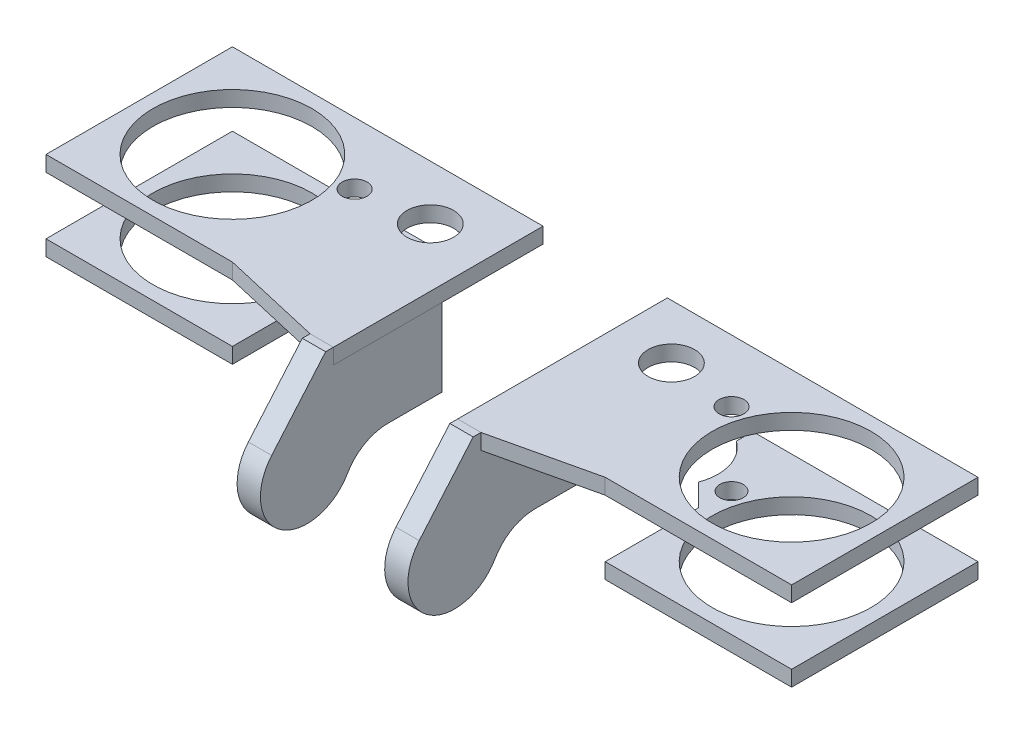
SolidWorks part; units mm, degrees
ref_plane "Front Plane" through (0, 0, 0) normal (0, 0, 1) x (1, 0, 0)
ref_plane "Top Plane" through (0, 0, 0) normal (0, 1, 0) x (1, 0, 0)
ref_plane "Right Plane" through (0, 0, 0) normal (1, 0, 0) x (0, 0, -1)
sketch "Sketch1" plane through (0, 0, 0) normal (0, 1, 0) x (1, 0, 0)
  line L0 (0, 0) -> (114.3, 0) construction
  line L1 (-114.3, 0) -> (0, 0) construction
  line L3 (-9.525, 184.15) -> (-3.175, 184.15)
  line L4 (-9.525, 184.15) -> (-9.525, 69.85)
  line L5 (-9.525, 69.85) -> (-3.175, 69.85)
  line L6 (-3.175, 184.15) -> (-3.175, 69.85)
  line L7 (-9.525, 184.15) -> (-3.175, 69.85) construction
  line L8 (-9.525, 69.85) -> (-3.175, 184.15) construction
  line L14 (-152.4, -76.2) -> (152.4, -76.2)
  line L18 (-114.3, 0) -> (-49.2756, 15.875) construction
  line L19 (49.2756, 15.875) -> (114.3, 0) construction
  line L20 (-25.4, 38.1) -> (0, 38.1) construction
  line L21 (-6.35, 127) -> (0, 127)
  line L29 (0, 0) -> (0, -25.4) construction
  line L30 (-114.3, 0) -> (-77.0346, 12.7) construction
  line L43 (-77.0346, 12.7) -> (-49.2756, 15.875) construction
  line L44 (49.2756, 15.875) -> (77.0346, 12.7) construction
  line L55 (77.0346, 12.7) -> (114.3, 0) construction
  line L69 (-152.4, -76.2) -> (-152.4, 38.1)
  line L70 (-152.4, 38.1) -> (152.4, 38.1)
  line L71 (152.4, -76.2) -> (152.4, 38.1)
  line L78 (0, 127) -> (0, -25.4)
  line L79 (0, -25.4) -> (0, -177.8) construction
  line L80 (-9.525, -234.95) -> (-3.175, -234.95) construction
  line L81 (-9.525, -234.95) -> (-9.525, -120.65) construction
  line L82 (-9.525, -120.65) -> (-3.175, -120.65) construction
  line L83 (-3.175, -234.95) -> (-3.175, -120.65) construction
  line L84 (-9.525, -234.95) -> (-3.175, -120.65) construction
  line L85 (-9.525, -120.65) -> (-3.175, -234.95) construction
  line L86 (0, -177.8) -> (-6.35, -177.8) construction
  line L87 (-34.925, -76.2) -> (-25.4, -76.2)
  line L88 (-34.925, -76.2) -> (-34.925, 38.1)
  line L89 (-34.925, 38.1) -> (-25.4, 38.1)
  line L90 (-25.4, -76.2) -> (-25.4, 38.1)
  line L91 (34.925, -76.2) -> (25.4, -76.2)
  line L92 (34.925, -76.2) -> (34.925, 38.1)
  line L93 (34.925, 38.1) -> (25.4, 38.1)
  line L94 (25.4, -76.2) -> (25.4, 38.1)
  line L95 (0, 38.1) -> (25.4, 38.1) construction
  circle A0 centre (-114.3, 0) radius 32.5
  circle A1 centre (-114.3, 0) radius 25
  circle A2 centre (114.3, 0) radius 32.5
  circle A3 centre (114.3, 0) radius 25
  circle A4 centre (-49.2756, 15.875) radius 17.5006
  circle A5 centre (49.2756, 15.875) radius 17.5006
  circle A6 centre (-77.0346, 12.7) radius 22.86
  circle A7 centre (77.0346, 12.7) radius 22.86
  point P8 (-6.35, 127)
  point P21 (114.3, 32.5)
  point P25 (49.2756, 33.3756)
  point P29 (49.2756, -1.6256)
  point P31 (0, -76.2)
  point P32 (-6.35, -177.8)
  point P62 (146.8, 0)
  dimension "D1" = 50
  dimension "D2" = 65
  dimension "D8" = 35.0012
  dimension "D11" = 152.4
  dimension "D12" = 63.5
  dimension "D17" = 45.72
  dimension "D3" = 114.3
  dimension "D4" = 6.35
  dimension "D5" = 228.6
  dimension "D6" = 38.1
  dimension "D7" = 38.1
  dimension "D9" = 114.3
  dimension "D10" = 9.525
  dimension "D13" = 9.525
  dimension "D14" = 50.8
  dimension "D15" = 27.94
  dimension "D16" = 39.37
  dimension "D18" = 22.225
  dimension "D19" = 25.4
sketch "Sketch2" plane through (0, 0, 0) normal (1, 0, 0) x (0, 0, -1)
  line L0 (0, 22.225) -> (0, 49.825) construction
  line L1 (-32.5, 53.325) -> (32.5, 53.325)
  line L2 (-32.5, 53.325) -> (-32.5, 46.325)
  line L3 (-32.5, 46.325) -> (32.5, 46.325)
  line L4 (32.5, 53.325) -> (32.5, 46.325)
  line L5 (-32.5, 53.325) -> (32.5, 46.325) construction
  line L6 (-32.5, 46.325) -> (32.5, 53.325) construction
  line L7 (-32.5, 82.55) -> (32.5, 82.55)
  line L8 (-32.5, 82.55) -> (-32.5, 75.55)
  line L9 (-32.5, 75.55) -> (32.5, 75.55)
  line L10 (32.5, 82.55) -> (32.5, 75.55)
  line L11 (-32.5, 82.55) -> (32.5, 75.55) construction
  line L12 (-32.5, 75.55) -> (32.5, 82.55) construction
  line L13 (-25.8191, 0) -> (33.9817, 0) construction
  line L14 (-25.4, 63.5) -> (-177.8, 63.5)
  line L15 (-76.2, 82.55) -> (38.1, 82.55)
  line L16 (-76.2, 82.55) -> (-76.2, 46.325)
  line L17 (-76.2, 46.325) -> (38.1, 46.325)
  line L18 (38.1, 82.55) -> (38.1, 46.325)
  line L19 (-25.4, 25.4) -> (-58.3956, 44.45) construction
  line L20 (-58.3956, 44.45) -> (-25.4, 63.5) construction
  line L21 (127, 0) -> (-25.4, 0) construction
  line L22 (-76.2, 76.2) -> (38.1, 76.2)
  line L23 (-76.2, 52.675) -> (38.1, 52.675)
  line L24 (-25.4, 25.4) -> (-25.4, 63.5) construction
  line L25 (-25.4, 7.62) -> (-25.4, 0) construction
  line L26 (32.5, 0) -> (-32.5, 0) construction
  line L40 (-1.6256, 31.6992) -> (33.3756, 31.6992)
  line L41 (-1.6256, 31.6992) -> (-1.6256, 76.2)
  line L42 (-1.6256, 76.2) -> (33.3756, 76.2)
  line L43 (33.3756, 31.6992) -> (33.3756, 76.2)
  line L44 (-1.6256, 31.6992) -> (33.3756, 76.2) construction
  line L45 (-1.6256, 76.2) -> (33.3756, 31.6992) construction
  line L46 (-38.1, 82.55) -> (-38.1, 46.325)
  line L47 (-38.1, 64.4375) -> (0, 64.4375) construction
  line L48 (0, 64.4375) -> (38.1, 64.4375) construction
  circle A0 centre (0, 22.225) radius 22.225
  circle A1 centre (-25.4, 63.5) radius 18.0086
  circle A2 centre (-25.4, 25.4) radius 17.78
  circle A3 centre (-177.8, 63.5) radius 57.15
  circle A4 centre (-25.4, 63.5) radius 4.7625
  circle A5 centre (-58.3956, 44.45) radius 17.78
  point P2 (0, 49.825)
  point P8 (0, 79.05)
  point P16 (-40.6156, 44.45)
  point P28 (-76.1756, 44.45)
  point P32 (15.875, 53.9496)
  point P34 (-234.95, 63.5)
  point P35 (-43.18, 25.4)
  point P36 (-7.62, 25.4)
  point P37 (-7.3914, 63.5)
  point P38 (-43.4086, 63.5)
  dimension "D1" = 44.45
  dimension "D8" = 36.0172
  dimension "D2" = 35.56
  dimension "D11" = 9.525
  dimension "D12" = 35.56
  dimension "D3" = 7
  dimension "D4" = 82.55
  dimension "D5" = 22.225
  dimension "D6" = 6.35
  dimension "D7" = 6.35
  dimension "D9" = 63.5
  dimension "D10" = 44.5008
  dimension "D13" = 38.1
  dimension "D14" = 38.1
  dimension "D15" = 38.1
sketch "Sketch5" plane through (0, 0, 0) normal (0, 1, 0) x (1, 0, 0)
  line L0 (-34.925, -76.2) -> (-34.925, 38.1) construction
  line L1 (-66.421, -7.62) -> (-34.925, -7.62)
  line L2 (-66.421, -7.62) -> (-66.421, -43.18)
  line L3 (-66.421, -43.18) -> (-34.925, -43.18)
  line L4 (-34.925, -7.62) -> (-34.925, -43.18)
  line L5 (-66.421, -7.62) -> (-34.925, -43.18) construction
  line L6 (-66.421, -43.18) -> (-34.925, -7.62) construction
  line L7 (-74.93, -40.6156) -> (-34.925, -40.6156)
  line L8 (-74.93, -40.6156) -> (-74.93, -76.1756)
  line L9 (-74.93, -76.1756) -> (-34.925, -76.1756)
  line L10 (-34.925, -40.6156) -> (-34.925, -76.1756)
  line L11 (-74.93, -40.6156) -> (-34.925, -76.1756) construction
  line L12 (-74.93, -76.1756) -> (-34.925, -40.6156) construction
  line L13 (-66.421, -7.3914) -> (-26.416, -7.3914)
  line L14 (-66.421, -7.3914) -> (-66.421, -43.4086)
  line L15 (-66.421, -43.4086) -> (-26.416, -43.4086)
  line L16 (-26.416, -7.3914) -> (-26.416, -43.4086)
  line L17 (-66.421, -7.3914) -> (-26.416, -43.4086) construction
  line L18 (-66.421, -43.4086) -> (-26.416, -7.3914) construction
  point P0 (-50.673, -25.4)
  point P5 (-54.9275, -58.3956)
  point P10 (-46.4185, -25.4)
  dimension "D2" = 31.496
  dimension "D5" = 40.005
  dimension "D6" = 40.005
ref_plane "Plane1" through (0, 76.2, 0) normal (0, 1, 0) x (1, 0, 0)
ref_plane "Plane2" through (0, 52.675, 0) normal (0, -1, 0) x (-1, 0, 0)
ref_plane "Plane3" through (25.4, 0, 0) normal (1, 0, 0) x (0, 0, -1)
sketch "Sketch6" plane through (25.4, 0, 0) normal (1, 0, 0) x (0, 0, -1)
  line L0 (-25.4, 25.4) -> (-25.4, 63.5) construction
  line L1 (-25.4, 25.4) -> (-58.3956, 44.45) construction
  line L2 (-72.8514, 56.8569) -> (-50.8, 82.55)
  line L3 (-76.2, 82.55) -> (38.1, 82.55) construction
  line L4 (-50.8, 82.55) -> (-47.625, 82.55)
  line L5 (-47.625, 82.55) -> (-47.625, 76.2)
  line L6 (-76.2, 76.2) -> (38.1, 76.2) construction
  line L7 (-47.625, 76.2) -> (-3.175, 76.2)
  line L8 (-3.175, 76.2) -> (-3.175, 44.45)
  line L9 (-3.175, 44.45) -> (-25.4, 44.45)
  arc A1 (-41.8978, 34.925) -> (-25.4, 44.45) centre (-25.4, 25.4) cw
  arc A2 (-41.8978, 34.925) -> (-72.8514, 56.8569) centre (-58.3956, 44.45) cw
  dimension "D1" = 22.225
  dimension "D2" = 22.225
  dimension "D3" = 3.175
extrude "Boss-Extrude1" add sketch "Sketch6" along normal up to vertex (9.525 mm away) up to point (34.925, 0, -38.1)
sketch "Sketch7" plane through (0, 76.2, 0) normal (0, 1, 0) x (1, 0, 0)
  line L0 (25.4, -47.625) -> (34.925, -47.625)
  line L2 (152.4, -76.2) -> (152.4, 38.1) construction
  line L3 (152.4, -38.1) -> (152.4, 38.1)
  line L4 (152.4, 38.1) -> (25.4, 38.1)
  line L5 (25.4, 38.1) -> (25.4, -47.625)
  line L6 (152.4, -38.1) -> (76.2, -38.1)
  line L7 (76.2, -38.1) -> (34.925, -47.625)
  line L8 (114.3, 38.1) -> (114.3, 0) construction
  line L9 (114.3, 0) -> (114.3, -38.1) construction
  circle A0 centre (114.3, 0) radius 32.5 construction
  circle A1 centre (114.3, 0) radius 32.5
  circle A2 centre (77.0346, 12.7) radius 5.08
  circle A3 centre (49.2756, 15.875) radius 9.525
  dimension "D1" = 10.16
  dimension "D2" = 19.05
extrude "Boss-Extrude2" add sketch "Sketch7" along normal up to surface (6.35 mm away) separate body up to face at (30.1625, 82.55, 49.2125)
sketch "Sketch8" plane through (0, 52.675, 0) normal (0, -1, 0) x (-1, 0, 0)
  line L0 (-60.325, 31.3932) -> (-60.325, 38.1)
  line L1 (-76.2, -38.1) -> (-152.4, -38.1)
  line L2 (-76.2, -38.1) -> (-76.2, 38.1) construction
  line L3 (-76.2, 38.1) -> (-152.4, 38.1)
  line L4 (-152.4, -38.1) -> (-152.4, 38.1)
  line L5 (-76.2, -38.1) -> (-152.4, 38.1) construction
  line L6 (-76.2, 38.1) -> (-152.4, -38.1) construction
  line L7 (152.4, 38.1) -> (-152.4, 38.1) construction
  line L8 (-60.325, 38.1) -> (-76.2, 38.1)
  line L9 (-76.2, -38.1) -> (-76.2, 0)
  line L10 (-76.2, 0) -> (-67.0856, 9.1144)
  line L11 (-34.925, -76.2) -> (-34.925, 38.1) construction
  circle A0 centre (-114.3, 0) radius 32.5 construction
  circle A1 centre (-114.3, 0) radius 32.5
  arc A2 (-67.0856, 9.1144) -> (-60.325, 31.3932) centre (-49.2756, 15.875) cw
  circle A3 centre (-77.0346, 12.7) radius 4.7625
  point P19 (-60.2806, 31.4247)
  point P22 (-77.0346, -15.706)
  point P23 (-77.0346, -4.1194)
  dimension "D1" = 9.525
  dimension "D2" = 19.05
  dimension "D3" = 25.4
  dimension "D4" = 45
  dimension "D5" = 38.1
extrude "Boss-Extrude3" add sketch "Sketch8" along normal up to vertex (6.35 mm away) separate body up to point (0, 46.325, -38.1)
mirror "Mirror2" about plane through (0, 0, 0) normal (1, 0, 0) of bodies 106 108 111
